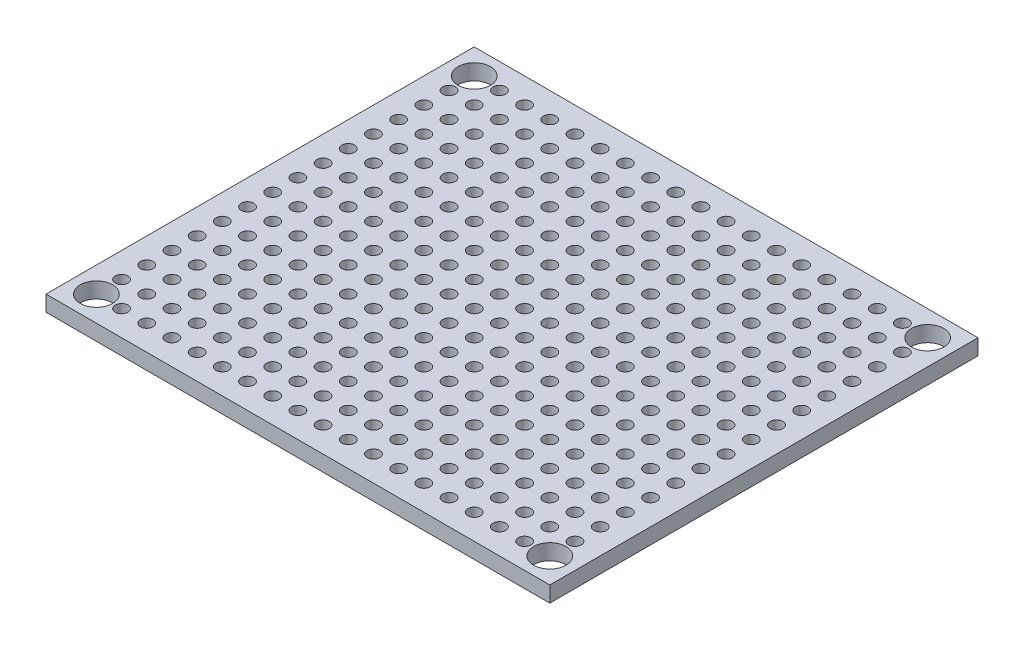
SolidWorks part; units mm, degrees
ref_plane "Front Plane" through (0, 0, 0) normal (0, 0, 1) x (1, 0, 0)
ref_plane "Top Plane" through (0, 0, 0) normal (0, 1, 0) x (1, 0, 0)
ref_plane "Right Plane" through (0, 0, 0) normal (1, 0, 0) x (0, 0, -1)
sketch "Sketch1" plane through (0, 0, 0) normal (0, 1, 0) x (1, 0, 0)
  line L1 (25.4, 21.59) -> (-25.4, 21.59)
  line L2 (25.4, 21.59) -> (25.4, -21.59)
  line L3 (25.4, -21.59) -> (-25.4, -21.59)
  line L4 (-25.4, 21.59) -> (-25.4, -21.59)
  line L5 (25.4, 21.59) -> (-25.4, -21.59) construction
  line L6 (25.4, -21.59) -> (-25.4, 21.59) construction
  point P0 (0, 0)
  dimension "D1" = 50.8
  dimension "D2" = 43.18
extrude "Boss-Extrude1" add sketch "Sketch1" along normal blind 1.5875
sketch "Sketch2" plane through (0, 1.5875, 0) normal (0, 1, 0) x (1, 0, 0)
  line L0 (-25.4, 21.59) -> (-25.4, -21.59) construction
  line L1 (-25.4, -21.59) -> (25.4, -21.59) construction
  circle A0 centre (-22.86, -19.05) radius 0.635
  circle A1 centre (-20.32, -19.05) radius 0.635
  circle A2 centre (-17.78, -19.05) radius 0.635
  circle A3 centre (-15.24, -19.05) radius 0.635
  circle A4 centre (-12.7, -19.05) radius 0.635
  circle A5 centre (-10.16, -19.05) radius 0.635
  circle A6 centre (-7.62, -19.05) radius 0.635
  circle A7 centre (-5.08, -19.05) radius 0.635
  circle A8 centre (-2.54, -19.05) radius 0.635
  circle A9 centre (0, -19.05) radius 0.635
  circle A10 centre (2.54, -19.05) radius 0.635
  circle A11 centre (5.08, -19.05) radius 0.635
  circle A12 centre (7.62, -19.05) radius 0.635
  circle A13 centre (10.16, -19.05) radius 0.635
  circle A14 centre (12.7, -19.05) radius 0.635
  circle A15 centre (15.24, -19.05) radius 0.635
  circle A16 centre (17.78, -19.05) radius 0.635
  circle A17 centre (20.32, -19.05) radius 0.635
  circle A18 centre (22.86, -19.05) radius 0.635
  circle A21 centre (-20.32, -16.51) radius 0.635
  circle A22 centre (-17.78, -16.51) radius 0.635
  circle A23 centre (-15.24, -16.51) radius 0.635
  circle A24 centre (-12.7, -16.51) radius 0.635
  circle A25 centre (-10.16, -16.51) radius 0.635
  circle A26 centre (-7.62, -16.51) radius 0.635
  circle A27 centre (-5.08, -16.51) radius 0.635
  circle A28 centre (-2.54, -16.51) radius 0.635
  circle A29 centre (0, -16.51) radius 0.635
  circle A30 centre (2.54, -16.51) radius 0.635
  circle A31 centre (5.08, -16.51) radius 0.635
  circle A32 centre (7.62, -16.51) radius 0.635
  circle A33 centre (10.16, -16.51) radius 0.635
  circle A34 centre (12.7, -16.51) radius 0.635
  circle A35 centre (15.24, -16.51) radius 0.635
  circle A36 centre (17.78, -16.51) radius 0.635
  circle A37 centre (20.32, -16.51) radius 0.635
  circle A38 centre (22.86, -16.51) radius 0.635
  circle A41 centre (-20.32, -13.97) radius 0.635
  circle A42 centre (-17.78, -13.97) radius 0.635
  circle A43 centre (-15.24, -13.97) radius 0.635
  circle A44 centre (-12.7, -13.97) radius 0.635
  circle A45 centre (-10.16, -13.97) radius 0.635
  circle A46 centre (-7.62, -13.97) radius 0.635
  circle A47 centre (-5.08, -13.97) radius 0.635
  circle A48 centre (-2.54, -13.97) radius 0.635
  circle A49 centre (0, -13.97) radius 0.635
  circle A50 centre (2.54, -13.97) radius 0.635
  circle A51 centre (5.08, -13.97) radius 0.635
  circle A52 centre (7.62, -13.97) radius 0.635
  circle A53 centre (10.16, -13.97) radius 0.635
  circle A54 centre (12.7, -13.97) radius 0.635
  circle A55 centre (15.24, -13.97) radius 0.635
  circle A56 centre (17.78, -13.97) radius 0.635
  circle A57 centre (20.32, -13.97) radius 0.635
  circle A58 centre (22.86, -13.97) radius 0.635
  circle A61 centre (-20.32, -11.43) radius 0.635
  circle A62 centre (-17.78, -11.43) radius 0.635
  circle A63 centre (-15.24, -11.43) radius 0.635
  circle A64 centre (-12.7, -11.43) radius 0.635
  circle A65 centre (-10.16, -11.43) radius 0.635
  circle A66 centre (-7.62, -11.43) radius 0.635
  circle A67 centre (-5.08, -11.43) radius 0.635
  circle A68 centre (-2.54, -11.43) radius 0.635
  circle A69 centre (0, -11.43) radius 0.635
  circle A70 centre (2.54, -11.43) radius 0.635
  circle A71 centre (5.08, -11.43) radius 0.635
  circle A72 centre (7.62, -11.43) radius 0.635
  circle A73 centre (10.16, -11.43) radius 0.635
  circle A74 centre (12.7, -11.43) radius 0.635
  circle A75 centre (15.24, -11.43) radius 0.635
  circle A76 centre (17.78, -11.43) radius 0.635
  circle A77 centre (20.32, -11.43) radius 0.635
  circle A78 centre (22.86, -11.43) radius 0.635
  circle A81 centre (-20.32, -8.89) radius 0.635
  circle A82 centre (-17.78, -8.89) radius 0.635
  circle A83 centre (-15.24, -8.89) radius 0.635
  circle A84 centre (-12.7, -8.89) radius 0.635
  circle A85 centre (-10.16, -8.89) radius 0.635
  circle A86 centre (-7.62, -8.89) radius 0.635
  circle A87 centre (-5.08, -8.89) radius 0.635
  circle A88 centre (-2.54, -8.89) radius 0.635
  circle A89 centre (0, -8.89) radius 0.635
  circle A90 centre (2.54, -8.89) radius 0.635
  circle A91 centre (5.08, -8.89) radius 0.635
  circle A92 centre (7.62, -8.89) radius 0.635
  circle A93 centre (10.16, -8.89) radius 0.635
  circle A94 centre (12.7, -8.89) radius 0.635
  circle A95 centre (15.24, -8.89) radius 0.635
  circle A96 centre (17.78, -8.89) radius 0.635
  circle A97 centre (20.32, -8.89) radius 0.635
  circle A98 centre (22.86, -8.89) radius 0.635
  circle A101 centre (-20.32, -6.35) radius 0.635
  circle A102 centre (-17.78, -6.35) radius 0.635
  circle A103 centre (-15.24, -6.35) radius 0.635
  circle A104 centre (-12.7, -6.35) radius 0.635
  circle A105 centre (-10.16, -6.35) radius 0.635
  circle A106 centre (-7.62, -6.35) radius 0.635
  circle A107 centre (-5.08, -6.35) radius 0.635
  circle A108 centre (-2.54, -6.35) radius 0.635
  circle A109 centre (0, -6.35) radius 0.635
  circle A110 centre (2.54, -6.35) radius 0.635
  circle A111 centre (5.08, -6.35) radius 0.635
  circle A112 centre (7.62, -6.35) radius 0.635
  circle A113 centre (10.16, -6.35) radius 0.635
  circle A114 centre (12.7, -6.35) radius 0.635
  circle A115 centre (15.24, -6.35) radius 0.635
  circle A116 centre (17.78, -6.35) radius 0.635
  circle A117 centre (20.32, -6.35) radius 0.635
  circle A118 centre (22.86, -6.35) radius 0.635
  circle A121 centre (-20.32, -3.81) radius 0.635
  circle A122 centre (-17.78, -3.81) radius 0.635
  circle A123 centre (-15.24, -3.81) radius 0.635
  circle A124 centre (-12.7, -3.81) radius 0.635
  circle A125 centre (-10.16, -3.81) radius 0.635
  circle A126 centre (-7.62, -3.81) radius 0.635
  circle A127 centre (-5.08, -3.81) radius 0.635
  circle A128 centre (-2.54, -3.81) radius 0.635
  circle A129 centre (0, -3.81) radius 0.635
  circle A130 centre (2.54, -3.81) radius 0.635
  circle A131 centre (5.08, -3.81) radius 0.635
  circle A132 centre (7.62, -3.81) radius 0.635
  circle A133 centre (10.16, -3.81) radius 0.635
  circle A134 centre (12.7, -3.81) radius 0.635
  circle A135 centre (15.24, -3.81) radius 0.635
  circle A136 centre (17.78, -3.81) radius 0.635
  circle A137 centre (20.32, -3.81) radius 0.635
  circle A138 centre (22.86, -3.81) radius 0.635
  circle A141 centre (-20.32, -1.27) radius 0.635
  circle A142 centre (-17.78, -1.27) radius 0.635
  circle A143 centre (-15.24, -1.27) radius 0.635
  circle A144 centre (-12.7, -1.27) radius 0.635
  circle A145 centre (-10.16, -1.27) radius 0.635
  circle A146 centre (-7.62, -1.27) radius 0.635
  circle A147 centre (-5.08, -1.27) radius 0.635
  circle A148 centre (-2.54, -1.27) radius 0.635
  circle A149 centre (0, -1.27) radius 0.635
  circle A150 centre (2.54, -1.27) radius 0.635
  circle A151 centre (5.08, -1.27) radius 0.635
  circle A152 centre (7.62, -1.27) radius 0.635
  circle A153 centre (10.16, -1.27) radius 0.635
  circle A154 centre (12.7, -1.27) radius 0.635
  circle A155 centre (15.24, -1.27) radius 0.635
  circle A156 centre (17.78, -1.27) radius 0.635
  circle A157 centre (20.32, -1.27) radius 0.635
  circle A158 centre (22.86, -1.27) radius 0.635
  circle A161 centre (-20.32, 1.27) radius 0.635
  circle A162 centre (-17.78, 1.27) radius 0.635
  circle A163 centre (-15.24, 1.27) radius 0.635
  circle A164 centre (-12.7, 1.27) radius 0.635
  circle A165 centre (-10.16, 1.27) radius 0.635
  circle A166 centre (-7.62, 1.27) radius 0.635
  circle A167 centre (-5.08, 1.27) radius 0.635
  circle A168 centre (-2.54, 1.27) radius 0.635
  circle A169 centre (0, 1.27) radius 0.635
  circle A170 centre (2.54, 1.27) radius 0.635
  circle A171 centre (5.08, 1.27) radius 0.635
  circle A172 centre (7.62, 1.27) radius 0.635
  circle A173 centre (10.16, 1.27) radius 0.635
  circle A174 centre (12.7, 1.27) radius 0.635
  circle A175 centre (15.24, 1.27) radius 0.635
  circle A176 centre (17.78, 1.27) radius 0.635
  circle A177 centre (20.32, 1.27) radius 0.635
  circle A178 centre (22.86, 1.27) radius 0.635
  circle A181 centre (-20.32, 3.81) radius 0.635
  circle A182 centre (-17.78, 3.81) radius 0.635
  circle A183 centre (-15.24, 3.81) radius 0.635
  circle A184 centre (-12.7, 3.81) radius 0.635
  circle A185 centre (-10.16, 3.81) radius 0.635
  circle A186 centre (-7.62, 3.81) radius 0.635
  circle A187 centre (-5.08, 3.81) radius 0.635
  circle A188 centre (-2.54, 3.81) radius 0.635
  circle A189 centre (0, 3.81) radius 0.635
  circle A190 centre (2.54, 3.81) radius 0.635
  circle A191 centre (5.08, 3.81) radius 0.635
  circle A192 centre (7.62, 3.81) radius 0.635
  circle A193 centre (10.16, 3.81) radius 0.635
  circle A194 centre (12.7, 3.81) radius 0.635
  circle A195 centre (15.24, 3.81) radius 0.635
  circle A196 centre (17.78, 3.81) radius 0.635
  circle A197 centre (20.32, 3.81) radius 0.635
  circle A198 centre (22.86, 3.81) radius 0.635
  circle A201 centre (-20.32, 6.35) radius 0.635
  circle A202 centre (-17.78, 6.35) radius 0.635
  circle A203 centre (-15.24, 6.35) radius 0.635
  circle A204 centre (-12.7, 6.35) radius 0.635
  circle A205 centre (-10.16, 6.35) radius 0.635
  circle A206 centre (-7.62, 6.35) radius 0.635
  circle A207 centre (-5.08, 6.35) radius 0.635
  circle A208 centre (-2.54, 6.35) radius 0.635
  circle A209 centre (0, 6.35) radius 0.635
  circle A210 centre (2.54, 6.35) radius 0.635
  circle A211 centre (5.08, 6.35) radius 0.635
  circle A212 centre (7.62, 6.35) radius 0.635
  circle A213 centre (10.16, 6.35) radius 0.635
  circle A214 centre (12.7, 6.35) radius 0.635
  circle A215 centre (15.24, 6.35) radius 0.635
  circle A216 centre (17.78, 6.35) radius 0.635
  circle A217 centre (20.32, 6.35) radius 0.635
  circle A218 centre (22.86, 6.35) radius 0.635
  circle A221 centre (-20.32, 8.89) radius 0.635
  circle A222 centre (-17.78, 8.89) radius 0.635
  circle A223 centre (-15.24, 8.89) radius 0.635
  circle A224 centre (-12.7, 8.89) radius 0.635
  circle A225 centre (-10.16, 8.89) radius 0.635
  circle A226 centre (-7.62, 8.89) radius 0.635
  circle A227 centre (-5.08, 8.89) radius 0.635
  circle A228 centre (-2.54, 8.89) radius 0.635
  circle A229 centre (0, 8.89) radius 0.635
  circle A230 centre (2.54, 8.89) radius 0.635
  circle A231 centre (5.08, 8.89) radius 0.635
  circle A232 centre (7.62, 8.89) radius 0.635
  circle A233 centre (10.16, 8.89) radius 0.635
  circle A234 centre (12.7, 8.89) radius 0.635
  circle A235 centre (15.24, 8.89) radius 0.635
  circle A236 centre (17.78, 8.89) radius 0.635
  circle A237 centre (20.32, 8.89) radius 0.635
  circle A238 centre (22.86, 8.89) radius 0.635
  circle A241 centre (-20.32, 11.43) radius 0.635
  circle A242 centre (-17.78, 11.43) radius 0.635
  circle A243 centre (-15.24, 11.43) radius 0.635
  circle A244 centre (-12.7, 11.43) radius 0.635
  circle A245 centre (-10.16, 11.43) radius 0.635
  circle A246 centre (-7.62, 11.43) radius 0.635
  circle A247 centre (-5.08, 11.43) radius 0.635
  circle A248 centre (-2.54, 11.43) radius 0.635
  circle A249 centre (0, 11.43) radius 0.635
  circle A250 centre (2.54, 11.43) radius 0.635
  circle A251 centre (5.08, 11.43) radius 0.635
  circle A252 centre (7.62, 11.43) radius 0.635
  circle A253 centre (10.16, 11.43) radius 0.635
  circle A254 centre (12.7, 11.43) radius 0.635
  circle A255 centre (15.24, 11.43) radius 0.635
  circle A256 centre (17.78, 11.43) radius 0.635
  circle A257 centre (20.32, 11.43) radius 0.635
  circle A258 centre (22.86, 11.43) radius 0.635
  circle A261 centre (-20.32, 13.97) radius 0.635
  circle A262 centre (-17.78, 13.97) radius 0.635
  circle A263 centre (-15.24, 13.97) radius 0.635
  circle A264 centre (-12.7, 13.97) radius 0.635
  circle A265 centre (-10.16, 13.97) radius 0.635
  circle A266 centre (-7.62, 13.97) radius 0.635
  circle A267 centre (-5.08, 13.97) radius 0.635
  circle A268 centre (-2.54, 13.97) radius 0.635
  circle A269 centre (0, 13.97) radius 0.635
  circle A270 centre (2.54, 13.97) radius 0.635
  circle A271 centre (5.08, 13.97) radius 0.635
  circle A272 centre (7.62, 13.97) radius 0.635
  circle A273 centre (10.16, 13.97) radius 0.635
  circle A274 centre (12.7, 13.97) radius 0.635
  circle A275 centre (15.24, 13.97) radius 0.635
  circle A276 centre (17.78, 13.97) radius 0.635
  circle A277 centre (20.32, 13.97) radius 0.635
  circle A278 centre (22.86, 13.97) radius 0.635
  circle A281 centre (-20.32, 16.51) radius 0.635
  circle A282 centre (-17.78, 16.51) radius 0.635
  circle A283 centre (-15.24, 16.51) radius 0.635
  circle A284 centre (-12.7, 16.51) radius 0.635
  circle A285 centre (-10.16, 16.51) radius 0.635
  circle A286 centre (-7.62, 16.51) radius 0.635
  circle A287 centre (-5.08, 16.51) radius 0.635
  circle A288 centre (-2.54, 16.51) radius 0.635
  circle A289 centre (0, 16.51) radius 0.635
  circle A290 centre (2.54, 16.51) radius 0.635
  circle A291 centre (5.08, 16.51) radius 0.635
  circle A292 centre (7.62, 16.51) radius 0.635
  circle A293 centre (10.16, 16.51) radius 0.635
  circle A294 centre (12.7, 16.51) radius 0.635
  circle A295 centre (15.24, 16.51) radius 0.635
  circle A296 centre (17.78, 16.51) radius 0.635
  circle A297 centre (20.32, 16.51) radius 0.635
  circle A298 centre (22.86, 16.51) radius 0.635
  circle A301 centre (-20.32, 19.05) radius 0.635
  circle A302 centre (-17.78, 19.05) radius 0.635
  circle A303 centre (-15.24, 19.05) radius 0.635
  circle A304 centre (-12.7, 19.05) radius 0.635
  circle A305 centre (-10.16, 19.05) radius 0.635
  circle A306 centre (-7.62, 19.05) radius 0.635
  circle A307 centre (-5.08, 19.05) radius 0.635
  circle A308 centre (-2.54, 19.05) radius 0.635
  circle A309 centre (0, 19.05) radius 0.635
  circle A310 centre (2.54, 19.05) radius 0.635
  circle A311 centre (5.08, 19.05) radius 0.635
  circle A312 centre (7.62, 19.05) radius 0.635
  circle A313 centre (10.16, 19.05) radius 0.635
  circle A314 centre (12.7, 19.05) radius 0.635
  circle A315 centre (15.24, 19.05) radius 0.635
  circle A316 centre (17.78, 19.05) radius 0.635
  circle A317 centre (20.32, 19.05) radius 0.635
  circle A318 centre (22.86, 19.05) radius 0.635
  circle A401 centre (-22.86, -16.51) radius 0.635
  circle A402 centre (-22.86, -13.97) radius 0.635
  circle A403 centre (-22.86, -11.43) radius 0.635
  circle A404 centre (-22.86, -8.89) radius 0.635
  circle A405 centre (-22.86, -6.35) radius 0.635
  circle A406 centre (-22.86, -3.81) radius 0.635
  circle A407 centre (-22.86, -1.27) radius 0.635
  circle A408 centre (-22.86, 1.27) radius 0.635
  circle A409 centre (-22.86, 3.81) radius 0.635
  circle A410 centre (-22.86, 6.35) radius 0.635
  circle A411 centre (-22.86, 8.89) radius 0.635
  circle A412 centre (-22.86, 11.43) radius 0.635
  circle A413 centre (-22.86, 13.97) radius 0.635
  circle A414 centre (-22.86, 16.51) radius 0.635
  circle A415 centre (-22.86, 19.05) radius 0.635
  dimension "D1" = 1.27
  dimension "D2" = 2.54
  dimension "D3" = 2.54
  dimension "D4" = 19
  dimension "D5" = 16
extrude "Cut-Extrude1" cut sketch "Sketch2" against normal blind 4.1275
ref_plane "Plane1" through (0, 0, 0) normal (-1, 0, 0) x (0, 0, 1)
ref_plane "Plane2" through (0, 0, 0) normal (0, 0, -1) x (-1, 0, 0)
hole_wizard "#4 Clearance Hole1" positions "Sketch3" profile "Sketch4" hole size "#4" standard "ANSI Inch" end condition through all
sketch "Sketch3" plane through (0, 1.5875, 0) normal (0, 1, 0) x (1, 0, 0)
  circle A3 centre (22.86, 19.05) radius 0.635 construction
  circle A4 centre (-22.86, 19.05) radius 0.635 construction
  circle A5 centre (-22.86, -19.05) radius 0.635 construction
  circle A6 centre (22.86, -19.05) radius 0.635 construction
  point P3 (-22.86, -19.05)
  point P6 (22.86, -19.05)
  point P13 (-22.86, 19.05)
  point P16 (22.86, 19.05)
sketch "Sketch4" plane through (-22.86, 1.5875, 19.05) normal (1, 0, 0) x (0, 0, 1)
  line L0 (0, 0) -> (0, 1.5875)
  line L1 (0, 1.5875) -> (1.6319, 1.5875)
  line L2 (1.6319, 1.5875) -> (1.6319, 0)
  line L5 (1.6319, 0) -> (0, 0)
  line L11 (0, -6.35) -> (0, 107.95) construction
  dimension "Thru Hole Dia." = 3.2639
  dimension "Thru Hole Depth" = 1.5875
